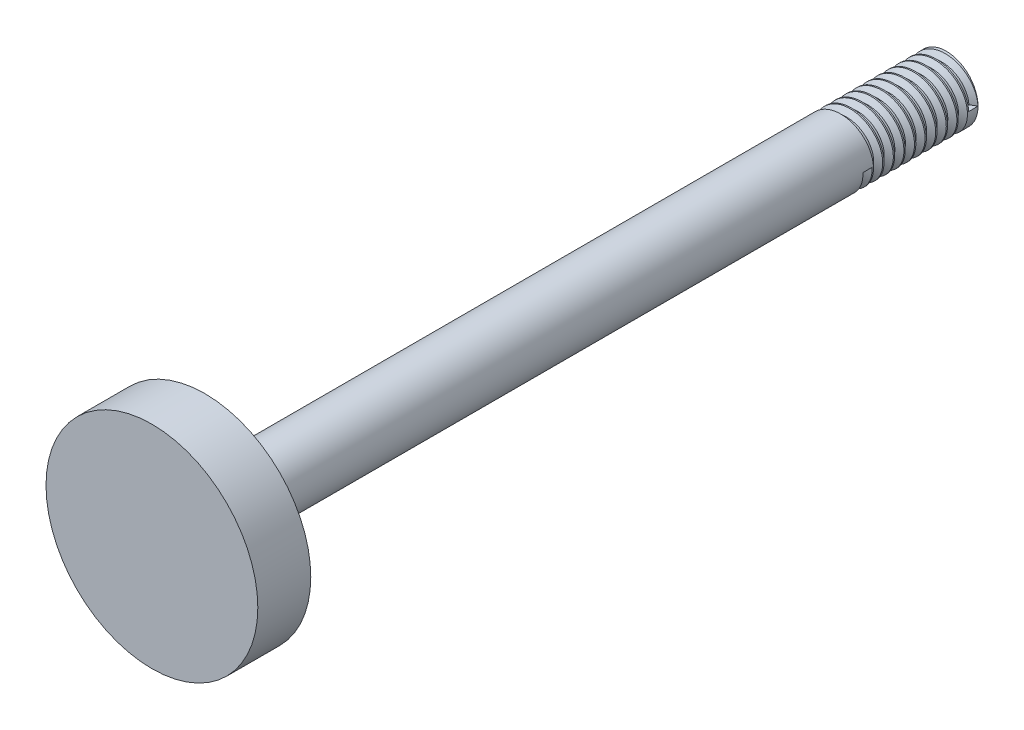
SolidWorks part; units mm, degrees
ref_plane "Front Plane" through (0, 0, 0) normal (0, 0, 1) x (1, 0, 0)
ref_plane "Top Plane" through (0, 0, 0) normal (0, 1, 0) x (1, 0, 0)
ref_plane "Right Plane" through (0, 0, 0) normal (1, 0, 0) x (0, 0, -1)
sketch "Sketch1" plane through (0, 0, 0) normal (0, 0, 1) x (1, 0, 0)
  circle A0 centre (0, 0) radius 10
  dimension "D1" = 20
extrude "Boss-Extrude1" add sketch "Sketch1" along normal blind 5
sketch "Sketch2" plane through (0, 0, 0) normal (0, 0, -1) x (-1, 0, 0)
  circle A0 centre (0, 0) radius 3
  dimension "D1" = 6
extrude "Boss-Extrude2" add sketch "Sketch2" along normal blind 70
thread "Thread1" pitch 1 method cut profile "Thread Profile1" start angle 0, offset 0, length 10, pitch 1, diameter 6
ref_plane "Plane1" through (3, 0, -70) normal (0, -1, 0) x (1, 0, 0)
sketch "Thread Profile1" plane through (3, 0, -70) normal (0, -1, 0) x (1, 0, 0)
  line L0 (0, 0) -> (0, 1) construction
  line L11 (0, 0) -> (0, 0.875)
  line L12 (0, 0.875) -> (-0.5413, 0.5625)
  line L13 (-0.5413, 0.5625) -> (-0.5413, 0.3125)
  line L15 (-0.5413, 0.3125) -> (0, 0)
  line L17 (-0.5413, 0.4375) -> (0, 0.4375) construction
  point P2 (0, 0)
  dimension "Pitch" = 1
  dimension "Profile_Angle" = 60
  dimension "Profile_Land" = 0.25
  dimension "Profile_Height" = 0.5413
